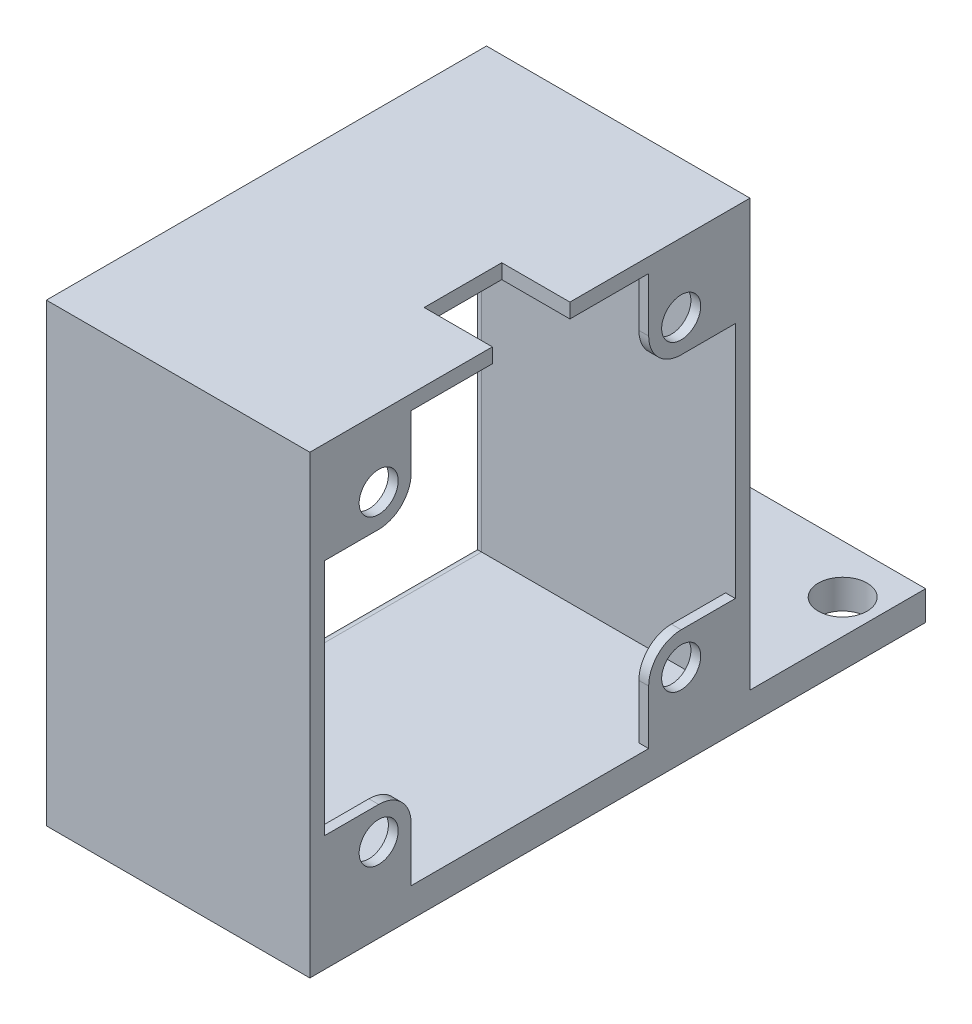
SolidWorks part; units mm, degrees
ref_plane "Front Plane" through (0, 0, 0) normal (0, 0, 1) x (1, 0, 0)
ref_plane "Top Plane" through (0, 0, 0) normal (0, 1, 0) x (1, 0, 0)
ref_plane "Right Plane" through (0, 0, 0) normal (1, 0, 0) x (0, 0, -1)
sketch "Sketch1" plane through (0, 0, 0) normal (0, 1, 0) x (1, 0, 0)
  line L1 (0, 0) -> (27, 0)
  line L2 (0, 0) -> (0, 63.1)
  line L3 (0, 63.1) -> (27, 63.1)
  line L4 (27, 0) -> (27, 63.1)
  circle A0 centre (3.5, 58.1) radius 2.5
  circle A1 centre (23.5, 58.1) radius 2.5
  dimension "D6" = 5
  dimension "D1" = 27
  dimension "D2" = 63.1
  dimension "D3" = 20
  dimension "D4" = 3.5
  dimension "D5" = 5
extrude "Boss-Extrude1" add sketch "Sketch1" along normal blind 3
sketch "Sketch2" plane through (0, 3, 0) normal (0, 1, 0) x (1, 0, 0)
  line L0 (0, 63.1) -> (0, 0) construction
  line L1 (27, 0) -> (0, 0)
  line L2 (27, 0) -> (27, 45.1)
  line L3 (27, 45.1) -> (0, 45.1)
  line L4 (0, 0) -> (0, 45.1)
  dimension "D1" = 45.1
extrude "Boss-Extrude2" add sketch "Sketch2" along normal blind 43.66
sketch "Sketch3" plane through (0, 0, 0) normal (-1, 0, 0) x (0, 0, 1)
  line L0 (-63.1, 0) -> (0, 0) construction
  line L1 (-43.6, 45.16) -> (-1.5, 45.16)
  line L2 (-43.6, 45.16) -> (-43.6, 3)
  line L3 (-43.6, 3) -> (-1.5, 3)
  line L4 (-1.5, 45.16) -> (-1.5, 3)
  line L5 (-45.1, 46.66) -> (-45.1, 3) construction
  line L6 (-45.1, 46.66) -> (0, 46.66) construction
  line L7 (0, 46.66) -> (0, 0) construction
  line L8 (-22.55, 3) -> (-22.55, 46.7088) construction
  line L11 (-43.6, 36.28) -> (-38.05, 36.28)
  line L12 (-34.72, 45.16) -> (-34.72, 39.61)
  line L13 (-10.38, 45.16) -> (-10.38, 39.61)
  line L14 (-1.5, 36.28) -> (-7.05, 36.28)
  line L17 (-43.6, 24.08) -> (11.7639, 24.08) construction
  line L20 (-1.5, 11.88) -> (-7.05, 11.88)
  line L21 (-10.38, 3) -> (-10.38, 8.55)
  line L22 (-34.72, 3) -> (-34.72, 8.55)
  line L23 (-43.6, 11.88) -> (-38.05, 11.88)
  line L24 (-43.6, 36.28) -> (-43.6, 45.16)
  arc A0 (-34.72, 39.61) -> (-38.05, 36.28) centre (-38.05, 39.61) cw
  arc A1 (-10.38, 39.61) -> (-7.05, 36.28) centre (-7.05, 39.61) ccw
  arc A2 (-10.38, 8.55) -> (-7.05, 11.88) centre (-7.05, 8.55) cw
  arc A3 (-34.72, 8.55) -> (-38.05, 11.88) centre (-38.05, 8.55) ccw
  circle A4 centre (-38.05, 8.55) radius 2
  circle A5 centre (-7.05, 39.61) radius 2
  circle A7 centre (-7.05, 8.55) radius 2
  circle A8 centre (-38.05, 39.61) radius 2
  point P17 (-34.72, 36.28)
  point P25 (-10.38, 36.28)
  point P38 (-10.38, 11.88)
  point P39 (-34.72, 11.88)
  dimension "D7" = 3.33
  dimension "D8" = 4
  dimension "D1" = 3
  dimension "D2" = 1.5
  dimension "D3" = 1.5
  dimension "D4" = 1.5
  dimension "D5" = 8.88
  dimension "D6" = 8.88
  dimension "D9" = 8.88
extrude "Cut-Extrude1" cut sketch "Sketch3" against normal through all contours A3 L22 L3 L21 A2 L20 L4 L14 A1 L13 L1 L12 A0 L11 L2 L23 region at (0, 24.08, -22.55)
extrude "Cut-Extrude2" cut sketch "Sketch3<8>" against normal offset from surface (26 mm away) 1 contours L22 A3 L23 L2 L3 | A0 L12 L1 L2 L11 | L13 A1 L14 L4 L1 | A2 L21 L3 L4 L20 region at (0, 41.0759, -39.5159) region at (0, 41.0759, -5.5841) region at (0, 7.0841, -39.5159) region at (0, 7.0841, -5.5841) up to face at (27, 16.5533, -36.0667)
sketch "Sketch3<8>" plane through (0, 0, 0) normal (-1, 0, 0) x (0, 0, 1) same geometry as "Sketch3"
fillet "Fillet2" [suppressed] radius 2
fillet "Fillet4" radius 1 4 edges at (0, 3, -22.55) (0, 24.08, -1.5) (0, 45.16, -22.55) (0, 24.08, -43.6)
sketch "Sketch6" plane through (0, 46.66, 0) normal (0, 1, 0) x (1, 0, 0)
  line L0 (0, 0) -> (27, 0) construction
  line L1 (20.015, 26.65) -> (27, 26.65)
  line L2 (20.015, 26.65) -> (20.015, 18.7)
  line L3 (20.015, 18.7) -> (27, 18.7)
  line L4 (27, 26.65) -> (27, 18.7)
  line L5 (27, 0) -> (27, 45.1) construction
  dimension "D1" = 18.7
  dimension "D2" = 7.95
  dimension "D3" = 0
  dimension "D4" = 6.985
extrude "Cut-Extrude3" cut sketch "Sketch6" against normal blind 1.5
extrude "Cut-Extrude4" cut sketch "Sketch3<9>" against normal through all contours A8 | A5 | A7 | A4 region at (0, 8.55, -38.05) region at (0, 39.61, -7.05) region at (0, 8.55, -7.05) region at (0, 39.61, -38.05)
sketch "Sketch3<9>" plane through (0, 0, 0) normal (-1, 0, 0) x (0, 0, 1) same geometry as "Sketch3"
